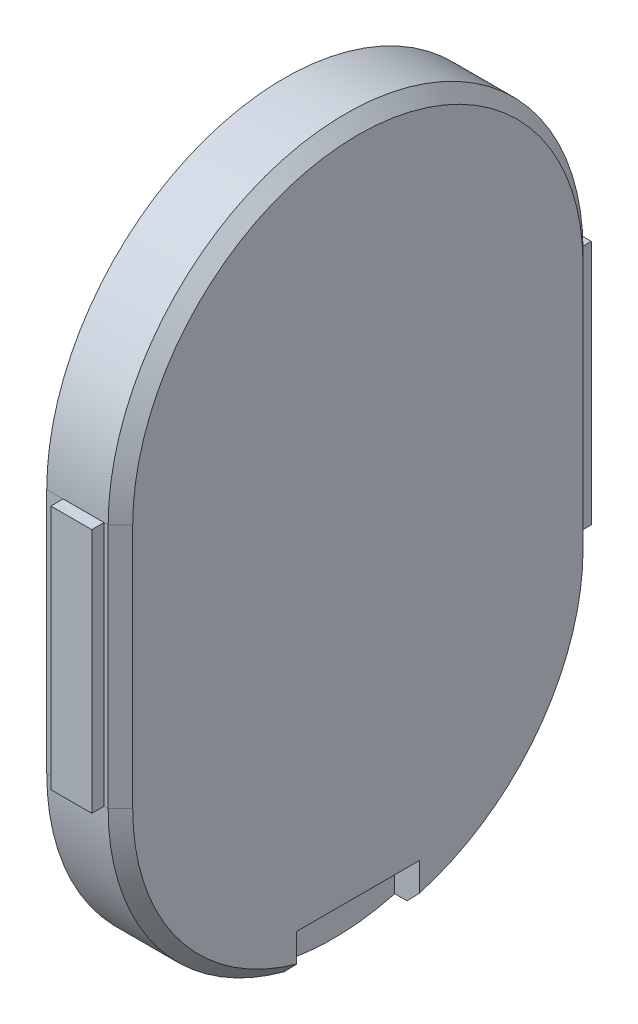
SolidWorks part; units mm, degrees
ref_plane "Front Plane" through (0, 0, 0) normal (0, 0, 1) x (1, 0, 0)
ref_plane "Top Plane" through (0, 0, 0) normal (0, 1, 0) x (1, 0, 0)
ref_plane "Right Plane" through (0, 0, 0) normal (1, 0, 0) x (0, 0, -1)
sketch "Sketch1" plane through (0, 0, 0) normal (1, 0, 0) x (0, 0, -1)
  line L0 (-94.1, 53) -> (-94.1, 59)
  line L1 (-82.5, 59) -> (-82.5, 53)
  arc A0 (-82.5, 53) -> (-88.3, 47.2) centre (-88.3, 53) cw
  arc A1 (-88.3, 47.2) -> (-94.1, 53) centre (-88.3, 53) cw
  arc A2 (-94.1, 59) -> (-88.3, 64.8) centre (-88.3, 59) cw
  arc A3 (-88.3, 64.8) -> (-82.5, 59) centre (-88.3, 59) cw
extrude "Boss-Extrude1" add sketch "Sketch1" along normal blind 1.8 from offset 36.2
chamfer "Chamfer1" distance 0.3 angle 45 4 edges at (38, 47.2, 88.3) (38, 56, 82.5) (38, 56, 94.1) (38, 64.8, 88.3)
sketch "Sketch2" plane through (0, 0, 0) normal (0, 0, 1) x (1, 0, 0)
  line L1 (36.6, 53) -> (37.6, 53)
  line L2 (36.6, 53) -> (36.6, 59)
  line L3 (36.6, 59) -> (37.6, 59)
  line L4 (37.6, 53) -> (37.6, 59)
extrude "Boss-Extrude2" add sketch "Sketch2" along normal blind 0.31 from offset 82.2
sketch "Sketch3" plane through (0, 0, 0) normal (0, 0, 1) x (1, 0, 0)
  line L1 (36.6, 53) -> (37.6, 53)
  line L2 (36.6, 53) -> (36.6, 59)
  line L3 (36.6, 59) -> (37.6, 59)
  line L4 (37.6, 53) -> (37.6, 59)
extrude "Boss-Extrude3" add sketch "Sketch3" along normal blind 0.31 from offset 94.09
sketch "Sketch4" plane through (0, 0, 0) normal (0, 0, 1) x (1, 0, 0)
  line L1 (37.4, 47.1) -> (38.1, 47.1)
  line L2 (37.4, 47.1) -> (37.4, 48.4)
  line L3 (37.4, 48.4) -> (38.1, 48.4)
  line L4 (38.1, 47.1) -> (38.1, 48.4)
extrude "Boss-Extrude4" add sketch "Sketch4" along normal blind 3 from offset 86.8 separate body
combine bodies "Combine1" operation type subtract main body 103 bodies to subtract 104
